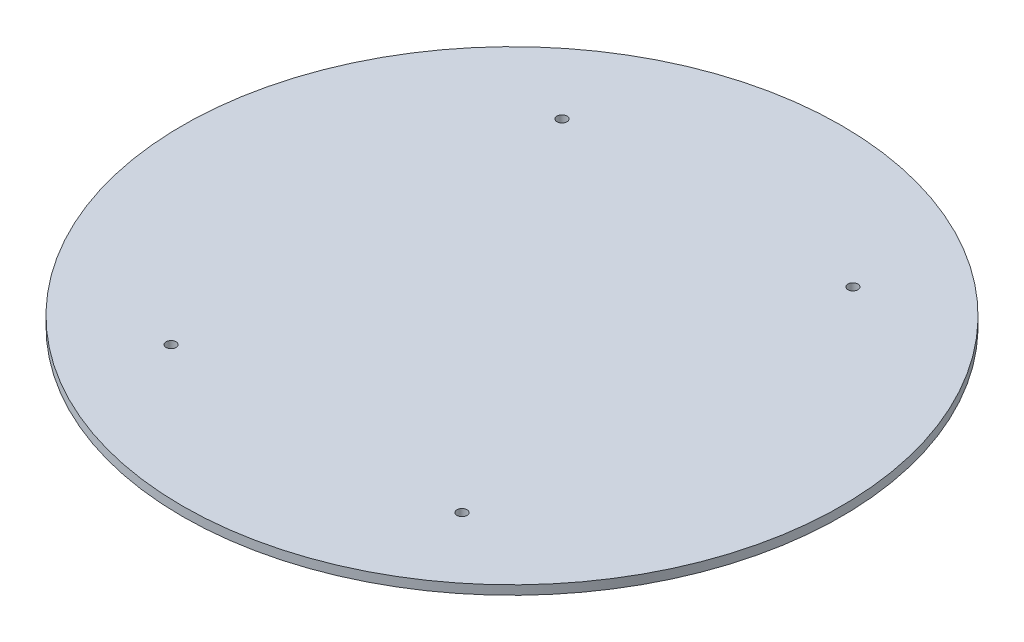
SolidWorks part; units mm, degrees
ref_plane "前视基准面" through (0, 0, 0) normal (0, 0, 1) x (1, 0, 0)
ref_plane "上视基准面" through (0, 0, 0) normal (0, 1, 0) x (1, 0, 0)
ref_plane "右视基准面" through (0, 0, 0) normal (1, 0, 0) x (0, 0, -1)
sketch "草图2" plane through (0, 0, 0) normal (0, 1, 0) x (1, 0, 0)
  circle A0 centre (0, 0) radius 72.5
  dimension "D1" = 145
extrude "凸台-拉伸1" add sketch "草图2" along normal blind 2
sketch "草图3" plane through (0, 0, 0) normal (0, -1, 0) x (1, 0, 0)
  line L1 (32, -43) -> (-32, -43) construction
  line L2 (32, -43) -> (32, 43) construction
  line L3 (32, 43) -> (-32, 43) construction
  line L4 (-32, -43) -> (-32, 43) construction
  line L5 (32, -43) -> (-32, 43) construction
  line L6 (32, 43) -> (-32, -43) construction
  circle A0 centre (32, 43) radius 1.1
  circle A1 centre (-32, 43) radius 1.1
  circle A2 centre (-32, -43) radius 1.1
  circle A4 centre (32, -43) radius 1.1
  point P0 (0, 0)
  dimension "D3" = 2.2
  dimension "D4" = 2.2
  dimension "D5" = 2.2
  dimension "D6" = 2.2
  dimension "D1" = 64
  dimension "D2" = 86
extrude "切除-拉伸1" cut sketch "草图3" against normal through all both and the other way through all
